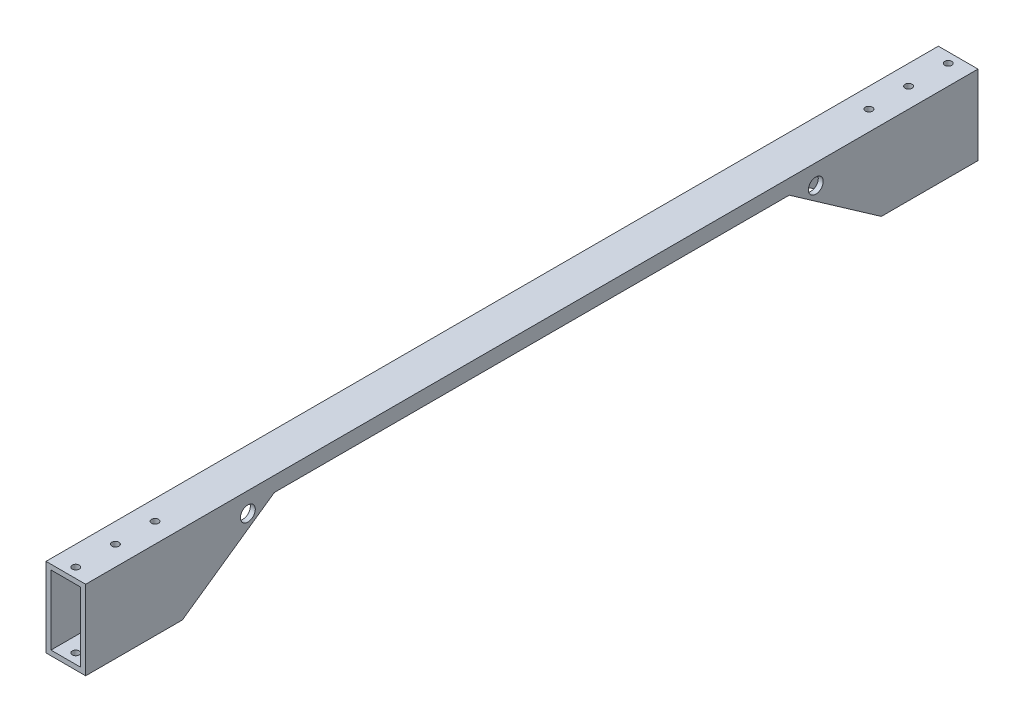
SolidWorks part; units mm, degrees
material "6061-T6 (SS)"
ref_plane "Front Plane" through (0, 0, 0) normal (0, 0, 1) x (1, 0, 0)
ref_plane "Top Plane" through (0, 0, 0) normal (0, 1, 0) x (1, 0, 0)
ref_plane "Right Plane" through (0, 0, 0) normal (1, 0, 0) x (0, 0, -1)
sketch "Sketch1" plane through (0, 0, 0) normal (0, 0, 1) x (1, 0, 0)
  line L1 (-12.7, -25.4) -> (12.7, -25.4)
  line L2 (-12.7, -25.4) -> (-12.7, 25.4)
  line L3 (-12.7, 25.4) -> (12.7, 25.4)
  line L4 (12.7, -25.4) -> (12.7, 25.4)
  line L5 (-12.7, -25.4) -> (12.7, 25.4) construction
  line L6 (-12.7, 25.4) -> (12.7, -25.4) construction
  point P0 (0, 0)
  dimension "D1" = 50.8
  dimension "D2" = 25.4
extrude "Extrude-Thin1" add sketch "Sketch1" along normal blind 571.5 thin thin type one direction reverse wall 3.175
hole_wizard "#8 Clearance Hole1" positions "3DSketch1" profile "Sketch3" hole size "#8" standard "ANSI Inch" end condition through all
sketch3d "3DSketch1"
  line L1 (12.7, 25.4, 0) -> (-12.7, 25.4, 0) construction
  line L6 (0, 25.4, 571.5) -> (0, 25.4, 0) construction
  line L7 (12.7, 25.4, 571.5) -> (-12.7, 25.4, 571.5) construction
  point P57 (0, 25.4, 6.35)
  point P59 (0, 25.4, 31.75)
  point P61 (0, 25.4, 57.15)
  point P63 (0, 25.4, 539.75)
  point P65 (0, 25.4, 514.35)
  point P67 (0, 25.4, 565.15)
  dimension "D1" = 25.4
  dimension "D2" = 25.4
  dimension "D3" = 6.35
  dimension "D4" = 25.4
  dimension "D5" = 25.4
  dimension "D6" = 6.35
sketch "Sketch3" plane through (0, 25.4, 565.15) normal (1, 0, 0) x (0, 0, 1)
  line L0 (0, 0) -> (0, 50.8)
  line L1 (0, 50.8) -> (2.2479, 50.8)
  line L2 (2.2479, 50.8) -> (2.2479, 0)
  line L5 (2.2479, 0) -> (0, 0)
  line L11 (0, -6.35) -> (0, 107.95) construction
  dimension "Thru Hole Dia." = 4.4958
  dimension "Thru Hole Depth" = 50.8
sketch "Sketch10" plane through (12.7, 0, 0) normal (1, 0, 0) x (0, 0, -1)
  line L0 (-509.5875, -25.4) -> (-450.6407, 15.875)
  line L2 (-571.5, -25.4) -> (0, -25.4) construction
  line L3 (-450.6407, 15.875) -> (-120.8593, 15.875)
  line L4 (-120.8593, 15.875) -> (-61.9125, -25.4)
  line L5 (-285.75, -25.4) -> (-285.75, 15.875) construction
  line L6 (-509.5875, -25.4) -> (-61.9125, -25.4)
  dimension "D1" = 447.675
  dimension "D2" = 41.275
  dimension "D3" = 35
extrude "Cut-Extrude1" cut sketch "Sketch10" against normal through all
hole_wizard "3/8 (0.375) Diameter Hole1" positions "Sketch11" profile "Sketch12" hole size "3/8" standard "ANSI Inch" end condition through all
sketch "Sketch11" plane through (-12.7, -44.45, 285.75) normal (1, 0, 0) x (0, 0, -1)
  point P0 (-181.864, 86.995)
  point P3 (-169.164, 78.74)
  point P6 (169.164, 78.74)
  point P9 (181.864, 86.995)
  point P12 (181.864, 57.15)
  point P15 (-181.864, 57.15)
sketch "Sketch12" plane through (-12.7, 42.545, 467.614) normal (0, 1, 0) x (0, 0, 1)
  line L0 (0, 0) -> (0, 25.4)
  line L1 (0, 25.4) -> (4.7625, 25.4)
  line L2 (4.7625, 25.4) -> (4.7625, 0)
  line L3 (4.7625, 0) -> (0, 0)
  line L4 (0, -6.35) -> (0, 107.95) construction
  dimension "Thru Hole Dia." = 9.525
  dimension "Thru Hole Depth" = 25.4
